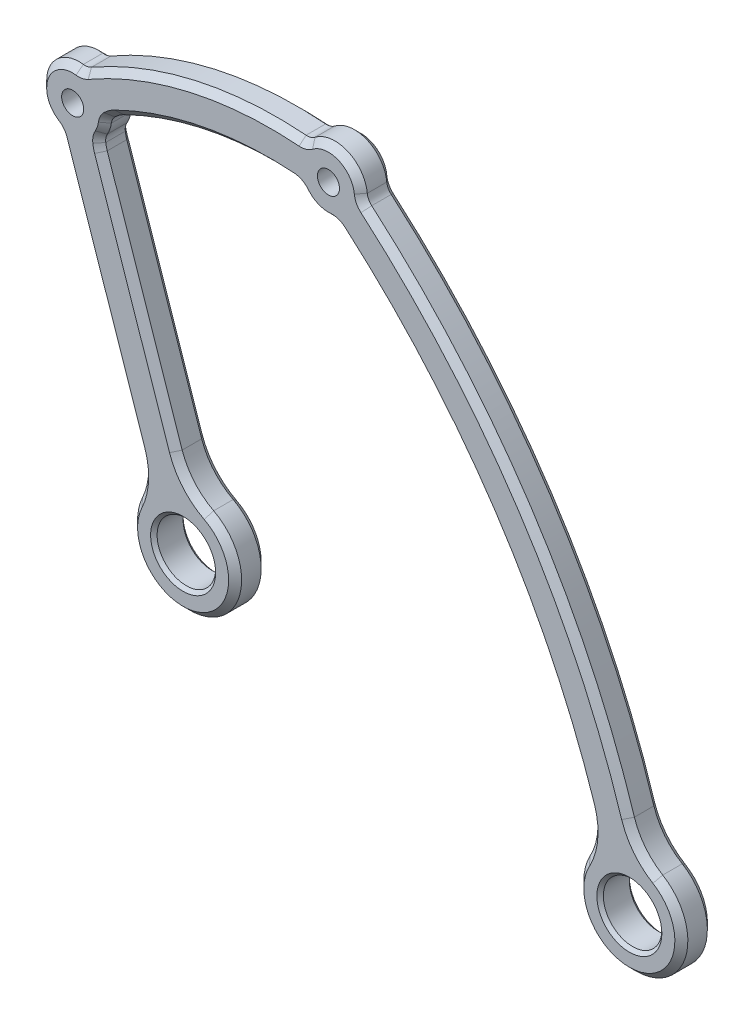
SolidWorks part; units mm, degrees
material "A2017"
ref_plane "正面" through (0, 0, 0) normal (0, 0, 1) x (1, 0, 0)
ref_plane "平面" through (0, 0, 0) normal (0, 1, 0) x (1, 0, 0)
ref_plane "右側面" through (0, 0, 0) normal (1, 0, 0) x (0, 0, -1)
sketch "ｽｹｯﾁ2" plane through (0, 0, 0) normal (0, 0, 1) x (1, 0, 0)
  line L4 (-103.4721, 101.9749) -> (-90.4656, 63.494)
  line L5 (-84.7815, 65.4152) -> (-96.3061, 99.5117)
  circle A0 centre (-91.0319, 74.5383) radius 1 construction
  circle A1 centre (-100.6248, 104.2316) radius 1
  circle A2 centre (-61.2846, 113.3479) radius 1
  circle A3 centre (-27.0948, 71.9322) radius 1 construction
  circle A21 centre (-100.6248, 104.2316) radius 1.5 construction
  circle A22 centre (-61.2846, 113.3479) radius 1.5 construction
  circle A23 centre (-91.0319, 74.5383) radius 1.5 construction
  circle A24 centre (-83.6371, 52.6602) radius 4.5
  circle A25 centre (-27.0948, 71.9322) radius 1.5 construction
  circle A26 centre (-15, 38.9143) radius 4.5
  arc A30 (-15.2219, 51.2935) -> (-57.8253, 114.4005) centre (-143.6936, 10.4967) ccw
  arc A31 (-57.8253, 114.4005) -> (-62.9665, 116.6163) centre (-64.1956, 106.6922) ccw
  arc A32 (-62.9665, 116.6163) -> (-64.6165, 116.798) centre (-70.4705, 56.0286) ccw
  arc A33 (-64.6165, 116.798) -> (-101.462, 107.7671) centre (-70.1265, 59.5994) ccw
  arc A34 (-101.462, 107.7671) -> (-103.4721, 101.9749) centre (-98.7354, 103.5759) ccw
  arc A35 (-90.8824, 56.0521) -> (-90.4656, 63.494) centre (-99.9391, 60.2919) ccw
  arc A36 (-90.8824, 56.0521) -> (-79.9353, 59.7522) centre (-83.6371, 52.6602) ccw
  arc A37 (-84.7815, 65.4152) -> (-79.9353, 59.7522) centre (-75.308, 68.6172) ccw
  arc A38 (-93.7791, 105.5979) -> (-96.3061, 99.5117) centre (-91.5694, 101.1127) ccw
  arc A39 (-65.8029, 110.8809) -> (-93.7791, 105.5979) centre (-70.2884, 57.9186) ccw
  arc A40 (-60.161, 108.5281) -> (-65.8029, 110.8809) centre (-66.6468, 100.9166) ccw
  arc A41 (-21.3117, 50.6279) -> (-60.161, 108.5281) centre (-143.6936, 10.4967) ccw
  arc A42 (-22.0284, 42.7355) -> (-21.3117, 50.6279) centre (-30.8139, 47.512) ccw
  arc A43 (-22.0284, 42.7355) -> (-10.8626, 45.7613) centre (-15, 38.9143) ccw
  arc A44 (-15.2219, 51.2935) -> (-10.8626, 45.7613) centre (-5.6909, 54.3201) ccw
  dimension "D1" = 9
  dimension "D2" = 2
extrude "ﾎﾞｽ - 押し出し1" add sketch "ｽｹｯﾁ2" along normal blind 5
hole_wizard "M3 すきま穴1" positions "ｽｹｯﾁ3" profile "ｽｹｯﾁ4" hole size "M3" standard "JIS" end condition through all
sketch "ｽｹｯﾁ3" plane through (0, 0, 5) normal (0, 0, 1) x (1, 0, 0)
  point P3 (-100.6248, 104.2316)
  point P6 (-61.2846, 113.3479)
sketch "ｽｹｯﾁ4" plane through (-100.6248, 104.2316, 5) normal (1, 0, 0) x (0, -1, 0)
  line L0 (0, 0) -> (0, 5)
  line L1 (0, 5) -> (1.7, 5)
  line L2 (1.7, 5) -> (1.7, 0)
  line L5 (1.7, 0) -> (0, 0)
  line L11 (0, -6.35) -> (0, 107.95) construction
  dimension "通し穴の直径" = 3.4
  dimension "通し穴の深さ" = 5
sketch "ｽｹｯﾁ5" plane through (0, 0, 5) normal (0, 0, 1) x (1, 0, 0)
  circle A3 centre (-61.2846, 113.3479) radius 5
  circle A5 centre (-100.6248, 104.2316) radius 5
  circle A6 centre (-61.2846, 113.3479) radius 1.7 construction
  circle A7 centre (-100.6248, 104.2316) radius 1.7 construction
  circle A8 centre (-61.2846, 113.3479) radius 1.7
  circle A9 centre (-100.6248, 104.2316) radius 1.7
  dimension "D1" = 10
extrude "ﾎﾞｽ - 押し出し2" add sketch "ｽｹｯﾁ5" against normal up to surface (5 mm away) up to face at (-98.9248, 104.2316, 0)
fillet "ﾌｨﾚｯﾄ1" radius 2 8 edges at (-65.6241, 110.8642, 2.5) (-60.1129, 108.4871, 2.5) (-64.8798, 116.8227, 2.5) (-99.3623, 109.0696, 2.5) (-102.6969, 99.6812, 2.5) (-96.5654, 101.3126, 2.5) (-95.6288, 104.0317, 2.5) (-56.2902, 113.1125, 2.5)
chamfer "面取り1" distance 1 angle 45 52 edges at (-94.4873, 105.1729, 0) (-80.5382, 110.0729, 0) (-95.4866, 104.1209, 0) (-65.8037, 110.7202, 0) (-95.8974, 102.6034, 0) (-63.2544, 108.7523, 0) (-96.5082, 101.1547, 0) (-60.0968, 108.2716, 0) (-96.4462, 100.0097, 0) (-36.4686, 81.8454, 0) (-90.5438, 82.4634, 0) (-20.8549, 46.6077, 0) (-82.9057, 62.1153, 0) (-12.9075, 31.1928, 0) (-81.0755, 45.0814, 0) (-13.5454, 48.1309, 0) (-89.9548, 59.7327, 0) (-31.1766, 84.7213, 0) (-96.456, 81.217, 0) (-56.0945, 113.1345, 0) (-102.7716, 99.5392, 0) (-59.3114, 117.9421, 0) (-105.3313, 105.9196, 0) (-64.9912, 116.9712, 0) (-99.3345, 109.2117, 0) (-82.7842, 115.6513, 0) (-99.3345, 109.2117, 5) (-105.3313, 105.9196, 5) (-82.7842, 115.6513, 5) (-102.7716, 99.5392, 5) (-64.9912, 116.9712, 5) (-96.456, 81.217, 5) (-59.3114, 117.9421, 5) (-89.9548, 59.7327, 5) (-56.0945, 113.1345, 5) (-81.0755, 45.0814, 5) (-31.1766, 84.7213, 5) (-82.9057, 62.1153, 5) (-13.5454, 48.1309, 5) (-90.5438, 82.4634, 5) (-12.9075, 31.1928, 5) (-96.4462, 100.0097, 5) (-20.8549, 46.6077, 5) (-96.5082, 101.1547, 5) (-36.4686, 81.8454, 5) (-95.8974, 102.6034, 5) (-60.0968, 108.2716, 5) (-95.4866, 104.1209, 5) (-63.2544, 108.7523, 5) (-94.4873, 105.1729, 5) (-65.8037, 110.7202, 5) (-80.5382, 110.0729, 5)
chamfer "面取り2" distance 0.5 angle 45 4 edges at (-79.1371, 52.6602, 0) (-79.1371, 52.6602, 5) (-10.5, 38.9143, 0) (-10.5, 38.9143, 5)
